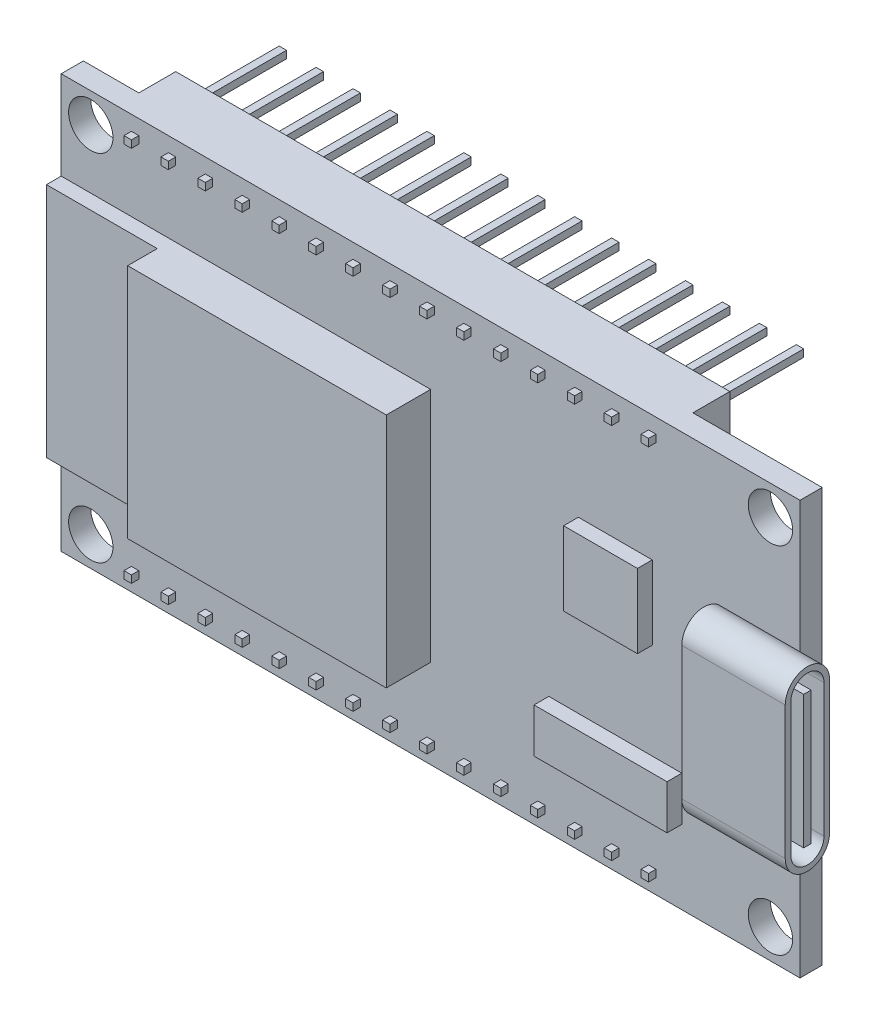
SolidWorks part; units mm, degrees
ref_plane "Front Plane" through (0, 0, 0) normal (0, 0, 1) x (1, 0, 0)
ref_plane "Top Plane" through (0, 0, 0) normal (0, 1, 0) x (1, 0, 0)
ref_plane "Right Plane" through (0, 0, 0) normal (1, 0, 0) x (0, 0, -1)
sketch "Sketch1" plane through (0, 0, 0) normal (0, 0, 1) x (1, 0, 0)
  line L0 (0, 0) -> (0, 14) construction
  line L1 (-25, -14) -> (25, -14)
  line L2 (-25, -14) -> (-25, 14)
  line L3 (-25, 14) -> (25, 14)
  line L4 (25, -14) -> (25, 14)
  line L5 (0, 14) -> (0, -14) construction
  line L6 (0, 0) -> (-25, 0) construction
  line L7 (-25, 0) -> (25, 0) construction
  line L8 (55, 0) -> (-55, 0) construction
  line L9 (-25, 14) -> (-23, 14)
  line L11 (-25, 14) -> (-23, 14)
  circle A4 centre (-23, 12) radius 1.5
  circle A5 centre (-23, -12) radius 1.5
  circle A6 centre (23, -12) radius 1.5
  circle A7 centre (23, 12) radius 1.5
  point P0 (0, 0)
  dimension "D5" = 3
  dimension "D1" = 50
  dimension "D2" = 28
  dimension "D3" = 2
extrude "Boss-Extrude1" add sketch "Sketch1" along normal mid plane 1.5 contours L1 L4 L3 L2 A5 A4 A6 A7 region at (0, 0, 0)
ref_plane "Plane1" through (27, 0, 0) normal (1, 0, 0) x (0, 0, -1)
sketch "Sketch5" plane through (27, 0, 0) normal (1, 0, 0) x (0, 0, -1)
  line L0 (0, -14) -> (0, 0)
  line L1 (-0.75, 0) -> (-2.25, 0)
  line L2 (-2.25, -4.5) -> (-2.25, 4.5) construction
  line L3 (-0.75, -14) -> (0.75, -14) construction
  line L4 (0, 0) -> (-0.75, 0)
  line L5 (-3.75, -4.5) -> (-3.75, 4.5)
  line L6 (-0.75, -4.5) -> (-0.75, 4.5)
  arc A0 (-3.75, -4.5) -> (-0.75, -4.5) centre (-2.25, -4.5) ccw
  arc A1 (-0.75, 4.5) -> (-3.75, 4.5) centre (-2.25, 4.5) ccw
  point P8 (-2.25, 0)
  dimension "D1" = 14
  dimension "D2" = 0.75
  dimension "D3" = 1.5
extrude "Boss-Extrude2" add sketch "Sketch5" against normal blind 7 contours L6 A1 L5 A0 region at (27, 0, 3.6263)
sketch "Sketch6" plane through (27, 0, 0) normal (1, 0, 0) x (0, 0, -1)
  line L0 (-2.25, 6) -> (-2.25, -6)
  line L1 (-2.25, -4.5) -> (-2.25, 4.5) construction
  line L2 (-2.5, -4.5) -> (-2, -4.5)
  line L13 (-2.5, -4.5) -> (-2.5, 4.5)
  line L14 (-2.5, 4.5) -> (-2, 4.5)
  line L15 (-2, -4.5) -> (-2, 4.5)
  line L16 (-2.5, -4.5) -> (-2, 4.5) construction
  line L17 (-2.5, 4.5) -> (-2, -4.5) construction
  line L18 (-3.375, -4.5) -> (-3.375, 4.5)
  line L19 (-1.125, -4.5) -> (-1.125, 4.5)
  arc A1 (-0.75, 4.5) -> (-3.75, 4.5) centre (-2.25, 4.5) ccw construction
  arc A2 (-3.75, -4.5) -> (-0.75, -4.5) centre (-2.25, -4.5) ccw construction
  arc A3 (-3.375, -4.5) -> (-1.125, -4.5) centre (-2.25, -4.5) ccw
  arc A4 (-1.125, 4.5) -> (-3.375, 4.5) centre (-2.25, 4.5) ccw
  point P8 (-2.25, 0)
  point P15 (-2.25, 0)
  dimension "D1" = 9
  dimension "D2" = 0.5
sketch "Sketch8" plane through (0, 0, 0.75) normal (0, 0, 1) x (1, 0, 0)
  line L0 (0, 14) -> (0, -14) construction
  line L1 (25, 14) -> (-25, 14) construction
  line L2 (-25, -14) -> (25, -14) construction
  line L3 (0, 8) -> (0, -8)
  line L4 (0, -8) -> (-17.5, -8)
  line L6 (0, 8) -> (-17.5, 8)
  line L7 (-17.5, -8) -> (-17.5, 8)
  line L8 (-25, 14) -> (-25, -14) construction
  line L9 (-17.5, 8) -> (-25, 8)
  line L10 (-17.5, 8) -> (-17.5, 14)
  line L11 (-17.5, 8) -> (-17.5, -8)
  line L12 (-17.5, -8) -> (-25, -8)
  line L13 (-25, 8) -> (-25, -8)
  line L14 (15, 5.5064) -> (15, 7.6756)
  line L19 (15, 0.5064) -> (15, 5.5064)
  line L20 (15, 5.5064) -> (10, 5.5064)
  line L21 (10, 0.5064) -> (10, 5.5064)
  line L24 (10, 0.5064) -> (15, 0.5064)
  line L27 (17, -5.995) -> (8, -5.995)
  line L28 (17, -5.995) -> (17, -8.995)
  line L29 (17, -8.995) -> (8, -8.995)
  line L30 (8, -5.995) -> (8, -8.995)
  line L39 (15, 14) -> (15, 12.75)
  line L40 (11.25, 11.5) -> (11.25, 14)
  line L41 (14.75, 13) -> (15.25, 13)
  line L42 (14.75, 13) -> (14.75, 12.5)
  line L47 (14.75, 12.5) -> (15.25, 12.5)
  line L48 (15.25, 13) -> (15.25, 12.5)
  line L49 (14.75, 13) -> (15.25, 12.5) construction
  line L50 (14.75, 12.5) -> (15.25, 13) construction
  line L51 (13.75, 11.5) -> (16.25, 11.5)
  line L52 (13.75, 11.5) -> (13.75, 14)
  line L53 (13.75, 14) -> (16.25, 14)
  line L54 (16.25, 11.5) -> (16.25, 14)
  line L55 (13.75, 11.5) -> (16.25, 14) construction
  line L56 (13.75, 14) -> (16.25, 11.5) construction
  line L57 (11.25, 11.5) -> (13.75, 11.5)
  line L58 (13.75, 11.5) -> (13.75, 14)
  line L59 (11.25, 14) -> (13.75, 14)
  line L60 (12.25, 13) -> (12.25, 12.5)
  line L61 (12.25, 13) -> (12.75, 13)
  line L62 (12.75, 13) -> (12.75, 12.5)
  line L63 (12.25, 12.5) -> (12.75, 12.5)
  line L64 (8.75, 11.5) -> (8.75, 14)
  line L65 (8.75, 11.5) -> (11.25, 11.5)
  line L66 (11.25, 11.5) -> (11.25, 14)
  line L67 (8.75, 14) -> (11.25, 14)
  line L68 (9.75, 13) -> (9.75, 12.5)
  line L69 (9.75, 13) -> (10.25, 13)
  line L70 (10.25, 13) -> (10.25, 12.5)
  line L71 (9.75, 12.5) -> (10.25, 12.5)
  line L72 (6.25, 11.5) -> (6.25, 14)
  line L73 (6.25, 11.5) -> (8.75, 11.5)
  line L74 (8.75, 11.5) -> (8.75, 14)
  line L75 (6.25, 14) -> (8.75, 14)
  line L76 (7.25, 13) -> (7.25, 12.5)
  line L77 (7.25, 13) -> (7.75, 13)
  line L78 (7.75, 13) -> (7.75, 12.5)
  line L79 (7.25, 12.5) -> (7.75, 12.5)
  line L80 (3.75, 11.5) -> (3.75, 14)
  line L81 (3.75, 11.5) -> (6.25, 11.5)
  line L82 (6.25, 11.5) -> (6.25, 14)
  line L83 (3.75, 14) -> (6.25, 14)
  line L84 (4.75, 13) -> (4.75, 12.5)
  line L85 (4.75, 13) -> (5.25, 13)
  line L86 (5.25, 13) -> (5.25, 12.5)
  line L87 (4.75, 12.5) -> (5.25, 12.5)
  line L88 (1.25, 11.5) -> (1.25, 14)
  line L89 (1.25, 11.5) -> (3.75, 11.5)
  line L90 (3.75, 11.5) -> (3.75, 14)
  line L91 (1.25, 14) -> (3.75, 14)
  line L92 (2.25, 13) -> (2.25, 12.5)
  line L93 (2.25, 13) -> (2.75, 13)
  line L94 (2.75, 13) -> (2.75, 12.5)
  line L95 (2.25, 12.5) -> (2.75, 12.5)
  line L96 (-1.25, 11.5) -> (-1.25, 14)
  line L97 (-1.25, 11.5) -> (1.25, 11.5)
  line L98 (1.25, 11.5) -> (1.25, 14)
  line L99 (-1.25, 14) -> (1.25, 14)
  line L100 (-0.25, 13) -> (-0.25, 12.5)
  line L101 (-0.25, 13) -> (0.25, 13)
  line L102 (0.25, 13) -> (0.25, 12.5)
  line L103 (-0.25, 12.5) -> (0.25, 12.5)
  line L104 (-3.75, 11.5) -> (-3.75, 14)
  line L105 (-3.75, 11.5) -> (-1.25, 11.5)
  line L106 (-1.25, 11.5) -> (-1.25, 14)
  line L107 (-3.75, 14) -> (-1.25, 14)
  line L108 (-2.75, 13) -> (-2.75, 12.5)
  line L109 (-2.75, 13) -> (-2.25, 13)
  line L110 (-2.25, 13) -> (-2.25, 12.5)
  line L111 (-2.75, 12.5) -> (-2.25, 12.5)
  line L112 (-6.25, 11.5) -> (-6.25, 14)
  line L113 (-6.25, 11.5) -> (-3.75, 11.5)
  line L114 (-3.75, 11.5) -> (-3.75, 14)
  line L115 (-6.25, 14) -> (-3.75, 14)
  line L116 (-5.25, 13) -> (-5.25, 12.5)
  line L117 (-5.25, 13) -> (-4.75, 13)
  line L118 (-4.75, 13) -> (-4.75, 12.5)
  line L119 (-5.25, 12.5) -> (-4.75, 12.5)
  line L120 (-8.75, 11.5) -> (-8.75, 14)
  line L121 (-8.75, 11.5) -> (-6.25, 11.5)
  line L122 (-6.25, 11.5) -> (-6.25, 14)
  line L123 (-8.75, 14) -> (-6.25, 14)
  line L124 (-7.75, 13) -> (-7.75, 12.5)
  line L125 (-7.75, 13) -> (-7.25, 13)
  line L126 (-7.25, 13) -> (-7.25, 12.5)
  line L127 (-7.75, 12.5) -> (-7.25, 12.5)
  line L128 (-11.25, 11.5) -> (-11.25, 14)
  line L129 (-11.25, 11.5) -> (-8.75, 11.5)
  line L130 (-8.75, 11.5) -> (-8.75, 14)
  line L131 (-11.25, 14) -> (-8.75, 14)
  line L132 (-10.25, 13) -> (-10.25, 12.5)
  line L133 (-10.25, 13) -> (-9.75, 13)
  line L134 (-9.75, 13) -> (-9.75, 12.5)
  line L135 (-10.25, 12.5) -> (-9.75, 12.5)
  line L136 (-13.75, 11.5) -> (-13.75, 14)
  line L137 (-13.75, 11.5) -> (-11.25, 11.5)
  line L138 (-11.25, 11.5) -> (-11.25, 14)
  line L139 (-13.75, 14) -> (-11.25, 14)
  line L140 (-12.75, 13) -> (-12.75, 12.5)
  line L141 (-12.75, 13) -> (-12.25, 13)
  line L142 (-12.25, 13) -> (-12.25, 12.5)
  line L143 (-12.75, 12.5) -> (-12.25, 12.5)
  line L144 (-16.25, 11.5) -> (-16.25, 14)
  line L145 (-16.25, 11.5) -> (-13.75, 11.5)
  line L146 (-13.75, 11.5) -> (-13.75, 14)
  line L147 (-16.25, 14) -> (-13.75, 14)
  line L148 (-15.25, 13) -> (-15.25, 12.5)
  line L149 (-15.25, 13) -> (-14.75, 13)
  line L150 (-14.75, 13) -> (-14.75, 12.5)
  line L151 (-15.25, 12.5) -> (-14.75, 12.5)
  line L152 (-18.75, 11.5) -> (-18.75, 14)
  line L153 (-18.75, 11.5) -> (-16.25, 11.5)
  line L154 (-16.25, 11.5) -> (-16.25, 14)
  line L155 (-18.75, 14) -> (-16.25, 14)
  line L156 (-17.75, 13) -> (-17.75, 12.5)
  line L157 (-17.75, 13) -> (-17.25, 13)
  line L158 (-17.25, 13) -> (-17.25, 12.5)
  line L159 (-17.75, 12.5) -> (-17.25, 12.5)
  line L160 (-21.25, 11.5) -> (-21.25, 14)
  line L161 (-21.25, 11.5) -> (-18.75, 11.5)
  line L162 (-18.75, 11.5) -> (-18.75, 14)
  line L163 (-21.25, 14) -> (-18.75, 14)
  line L164 (-20.25, 13) -> (-20.25, 12.5)
  line L165 (-20.25, 13) -> (-19.75, 13)
  line L166 (-19.75, 13) -> (-19.75, 12.5)
  line L167 (-20.25, 12.5) -> (-19.75, 12.5)
  line L168 (0, 0) -> (17, 0) construction
  line L169 (17, 0) -> (-25, 0) construction
  line L170 (14.75, -12.5) -> (15.25, -12.5)
  line L171 (15.25, -13) -> (15.25, -12.5)
  line L172 (14.75, -13) -> (15.25, -13)
  line L173 (14.75, -13) -> (14.75, -12.5)
  line L174 (13.75, -14) -> (16.25, -14)
  line L175 (16.25, -11.5) -> (16.25, -14)
  line L176 (13.75, -11.5) -> (16.25, -11.5)
  line L177 (13.75, -11.5) -> (13.75, -14)
  line L178 (11.25, -14) -> (13.75, -14)
  line L179 (13.75, -11.5) -> (13.75, -14)
  line L180 (11.25, -11.5) -> (13.75, -11.5)
  line L181 (11.25, -11.5) -> (11.25, -14)
  line L182 (12.25, -12.5) -> (12.75, -12.5)
  line L183 (12.75, -13) -> (12.75, -12.5)
  line L184 (12.25, -13) -> (12.75, -13)
  line L185 (12.25, -13) -> (12.25, -12.5)
  line L186 (8.75, -14) -> (11.25, -14)
  line L187 (11.25, -11.5) -> (11.25, -14)
  line L188 (8.75, -11.5) -> (11.25, -11.5)
  line L189 (8.75, -11.5) -> (8.75, -14)
  line L190 (9.75, -12.5) -> (10.25, -12.5)
  line L191 (10.25, -13) -> (10.25, -12.5)
  line L192 (9.75, -13) -> (10.25, -13)
  line L193 (9.75, -13) -> (9.75, -12.5)
  line L194 (6.25, -14) -> (8.75, -14)
  line L195 (8.75, -11.5) -> (8.75, -14)
  line L196 (6.25, -11.5) -> (8.75, -11.5)
  line L197 (6.25, -11.5) -> (6.25, -14)
  line L198 (7.25, -12.5) -> (7.75, -12.5)
  line L199 (7.75, -13) -> (7.75, -12.5)
  line L200 (7.25, -13) -> (7.75, -13)
  line L201 (7.25, -13) -> (7.25, -12.5)
  line L202 (3.75, -14) -> (6.25, -14)
  line L203 (6.25, -11.5) -> (6.25, -14)
  line L204 (3.75, -11.5) -> (6.25, -11.5)
  line L205 (3.75, -11.5) -> (3.75, -14)
  line L206 (4.75, -12.5) -> (5.25, -12.5)
  line L207 (5.25, -13) -> (5.25, -12.5)
  line L208 (4.75, -13) -> (5.25, -13)
  line L209 (4.75, -13) -> (4.75, -12.5)
  line L210 (1.25, -14) -> (3.75, -14)
  line L211 (3.75, -11.5) -> (3.75, -14)
  line L212 (1.25, -11.5) -> (3.75, -11.5)
  line L213 (1.25, -11.5) -> (1.25, -14)
  line L214 (2.25, -12.5) -> (2.75, -12.5)
  line L215 (2.75, -13) -> (2.75, -12.5)
  line L216 (2.25, -13) -> (2.75, -13)
  line L217 (2.25, -13) -> (2.25, -12.5)
  line L218 (-1.25, -14) -> (1.25, -14)
  line L219 (1.25, -11.5) -> (1.25, -14)
  line L220 (-1.25, -11.5) -> (1.25, -11.5)
  line L221 (-1.25, -11.5) -> (-1.25, -14)
  line L222 (-0.25, -12.5) -> (0.25, -12.5)
  line L223 (0.25, -13) -> (0.25, -12.5)
  line L224 (-0.25, -13) -> (0.25, -13)
  line L225 (-0.25, -13) -> (-0.25, -12.5)
  line L226 (-3.75, -14) -> (-1.25, -14)
  line L227 (-1.25, -11.5) -> (-1.25, -14)
  line L228 (-3.75, -11.5) -> (-1.25, -11.5)
  line L229 (-3.75, -11.5) -> (-3.75, -14)
  line L230 (-2.75, -12.5) -> (-2.25, -12.5)
  line L231 (-2.25, -13) -> (-2.25, -12.5)
  line L232 (-2.75, -13) -> (-2.25, -13)
  line L233 (-2.75, -13) -> (-2.75, -12.5)
  line L234 (-6.25, -14) -> (-3.75, -14)
  line L235 (-3.75, -11.5) -> (-3.75, -14)
  line L236 (-6.25, -11.5) -> (-3.75, -11.5)
  line L237 (-6.25, -11.5) -> (-6.25, -14)
  line L238 (-5.25, -12.5) -> (-4.75, -12.5)
  line L239 (-4.75, -13) -> (-4.75, -12.5)
  line L240 (-5.25, -13) -> (-4.75, -13)
  line L241 (-5.25, -13) -> (-5.25, -12.5)
  line L242 (-8.75, -14) -> (-6.25, -14)
  line L243 (-6.25, -11.5) -> (-6.25, -14)
  line L244 (-8.75, -11.5) -> (-6.25, -11.5)
  line L245 (-8.75, -11.5) -> (-8.75, -14)
  line L246 (-7.75, -12.5) -> (-7.25, -12.5)
  line L247 (-7.25, -13) -> (-7.25, -12.5)
  line L248 (-7.75, -13) -> (-7.25, -13)
  line L249 (-7.75, -13) -> (-7.75, -12.5)
  line L250 (-11.25, -14) -> (-8.75, -14)
  line L251 (-8.75, -11.5) -> (-8.75, -14)
  line L252 (-11.25, -11.5) -> (-8.75, -11.5)
  line L253 (-11.25, -11.5) -> (-11.25, -14)
  line L254 (-10.25, -12.5) -> (-9.75, -12.5)
  line L255 (-9.75, -13) -> (-9.75, -12.5)
  line L256 (-10.25, -13) -> (-9.75, -13)
  line L257 (-10.25, -13) -> (-10.25, -12.5)
  line L258 (-13.75, -14) -> (-11.25, -14)
  line L259 (-11.25, -11.5) -> (-11.25, -14)
  line L260 (-13.75, -11.5) -> (-11.25, -11.5)
  line L261 (-13.75, -11.5) -> (-13.75, -14)
  line L262 (-12.75, -12.5) -> (-12.25, -12.5)
  line L263 (-12.25, -13) -> (-12.25, -12.5)
  line L264 (-12.75, -13) -> (-12.25, -13)
  line L265 (-12.75, -13) -> (-12.75, -12.5)
  line L266 (-16.25, -14) -> (-13.75, -14)
  line L267 (-13.75, -11.5) -> (-13.75, -14)
  line L268 (-16.25, -11.5) -> (-13.75, -11.5)
  line L269 (-16.25, -11.5) -> (-16.25, -14)
  line L270 (-15.25, -12.5) -> (-14.75, -12.5)
  line L271 (-14.75, -13) -> (-14.75, -12.5)
  line L272 (-15.25, -13) -> (-14.75, -13)
  line L273 (-15.25, -13) -> (-15.25, -12.5)
  line L274 (-18.75, -14) -> (-16.25, -14)
  line L275 (-16.25, -11.5) -> (-16.25, -14)
  line L276 (-18.75, -11.5) -> (-16.25, -11.5)
  line L277 (-18.75, -11.5) -> (-18.75, -14)
  line L278 (-17.75, -12.5) -> (-17.25, -12.5)
  line L279 (-17.25, -13) -> (-17.25, -12.5)
  line L280 (-17.75, -13) -> (-17.25, -13)
  line L281 (-17.75, -13) -> (-17.75, -12.5)
  line L282 (-21.25, -14) -> (-18.75, -14)
  line L283 (-18.75, -11.5) -> (-18.75, -14)
  line L284 (-21.25, -11.5) -> (-18.75, -11.5)
  line L285 (-21.25, -11.5) -> (-21.25, -14)
  line L286 (-20.25, -12.5) -> (-19.75, -12.5)
  line L287 (-19.75, -13) -> (-19.75, -12.5)
  line L288 (-20.25, -13) -> (-19.75, -13)
  line L289 (-20.25, -13) -> (-20.25, -12.5)
  point P6 (0, 0)
  dimension "D1" = 17.5
  dimension "D2" = 16
  dimension "D3" = 6
  dimension "D4" = 5
  dimension "D5" = 5
  dimension "D6" = 9
  dimension "D7" = 3
  dimension "D8" = 1.25
  dimension "D9" = 0.5
  dimension "D10" = 0.5
  dimension "D11" = 2.5
  dimension "D12" = 15
  dimension "D13" = 15
extrude "Boss-Extrude3" add sketch "Sketch8" against normal blind 4 contours L176 L177 L175 L172 L173 L170 L171 | L180 L181 L177 L184 L185 L182 L183 | L188 L189 L181 L192 L193 L190 L191 | L196 L197 L189 L200 L201 L198 L199 | L204 L205 L197 L208 L209 L206 L207 | L212 L213 L205 L216 L217 L214 L215 | L220 L221 L213 L224 L225 L222 L223 | L228 L229 L221 L232 L233 L230 L231 | L236 L237 L229 L240 L241 L238 L239 | L244 L245 L237 L248 L249 L246 L247 | L252 L253 L245 L256 L257 L254 L255 | L260 L261 L253 L264 L265 L262 L263 | L268 L269 L261 L272 L273 L270 L271 | L276 L277 L269 L280 L281 L278 L279 | L284 L285 L277 L288 L289 L286 L287 | L160 L161 L152 L167 L164 L165 L166 | L159 L10 L153 L144 L157 L158 | L159 L156 L157 L10 L152 L153 | L144 L145 L136 L151 L148 L149 L150 | L136 L137 L128 L143 L140 L141 L142 | L128 L129 L120 L135 L132 L133 L134 | L120 L121 L112 L127 L124 L125 L126 | L112 L113 L104 L119 L116 L117 L118 | L96 L97 L88 L103 L100 L101 L102 | L88 L89 L80 L95 L92 L93 L94 | L80 L81 L72 L87 L84 L85 L86 | L72 L73 L64 L79 L76 L77 L78 | L64 L65 L40 L71 L68 L69 L70 | L40 L57 L52 L63 L60 L61 L62 | L51 L54 L41 L48 L47 L42 L52 | L104 L107 L106 L105 region at (-18.1458, 12.75, 0.75) region at (-16.8542, 12.75, 0.75) region at (-20, 11.5354, 0.75) region at (-16.2146, 12.75, 0.75) region at (-13.7146, 12.75, 0.75) region at (-11.2146, 12.75, 0.75) region at (-8.7146, 12.75, 0.75) region at (-6.2146, 12.75, 0.75) region at (-1.2146, 12.75, 0.75) region at (1.2854, 12.75, 0.75) region at (3.7854, 12.75, 0.75) region at (6.2854, 12.75, 0.75) region at (8.7854, 12.75, 0.75) region at (11.2854, 12.75, 0.75) region at (13.7854, 12.75, 0.75) region at (13.7854, -12.75, 0.75) region at (12.5, -13.9646, 0.75) region at (10, -13.9646, 0.75) region at (7.5, -13.9646, 0.75) region at (5, -13.9646, 0.75) region at (2.5, -13.9646, 0.75) region at (0, -13.9646, 0.75) region at (-2.5, -13.9646, 0.75) region at (-5, -13.9646, 0.75) region at (-7.5, -13.9646, 0.75) region at (-10, -13.9646, 0.75) region at (-12.5, -13.9646, 0.75) region at (-15, -13.9646, 0.75) region at (-17.5, -13.9646, 0.75) region at (-20, -13.9646, 0.75)
extrude "Boss-Extrude4" add sketch "Sketch8<3>" along normal blind 0.5 and the other way blind 10 contours L172 L171 L170 L173
sketch "Sketch8<3>" plane through (0, 0, 0.75) normal (0, 0, 1) x (1, 0, 0) same geometry as "Sketch8"
pattern_linear "LPattern1" count 15 spacing 2.5 along (-1, 0, 0) of "Boss-Extrude4"
mirror "Mirror1" about plane through (0, 0, 0) normal (0, 1, 0) of "LPattern1"
extrude "Boss-Extrude5" add sketch "Sketch8<4>" along normal blind 3 contours L7 L4 L3 L6 region at (-8.75, 0, 0.75)
sketch "Sketch8<4>" plane through (0, 0, 0.75) normal (0, 0, 1) x (1, 0, 0) same geometry as "Sketch8"
extrude "Boss-Extrude6" add sketch "Sketch8<5>" along normal blind 1 contours L12 L7 L9 | L28 L27 L30 L29 | L19 L20 L21 L24 region at (-21.25, 0, 0.75)
sketch "Sketch8<5>" plane through (0, 0, 0.75) normal (0, 0, 1) x (1, 0, 0) same geometry as "Sketch8"
extrude "Cut-Extrude4" cut sketch "Sketch6" against normal blind 6 contours L0 A4 L18 A3 L2 L13 L14 | L19 A4 L0 L14 L15 L2 A3 region at (27, 0, 1.6048) region at (27, 0, 2.8952)
